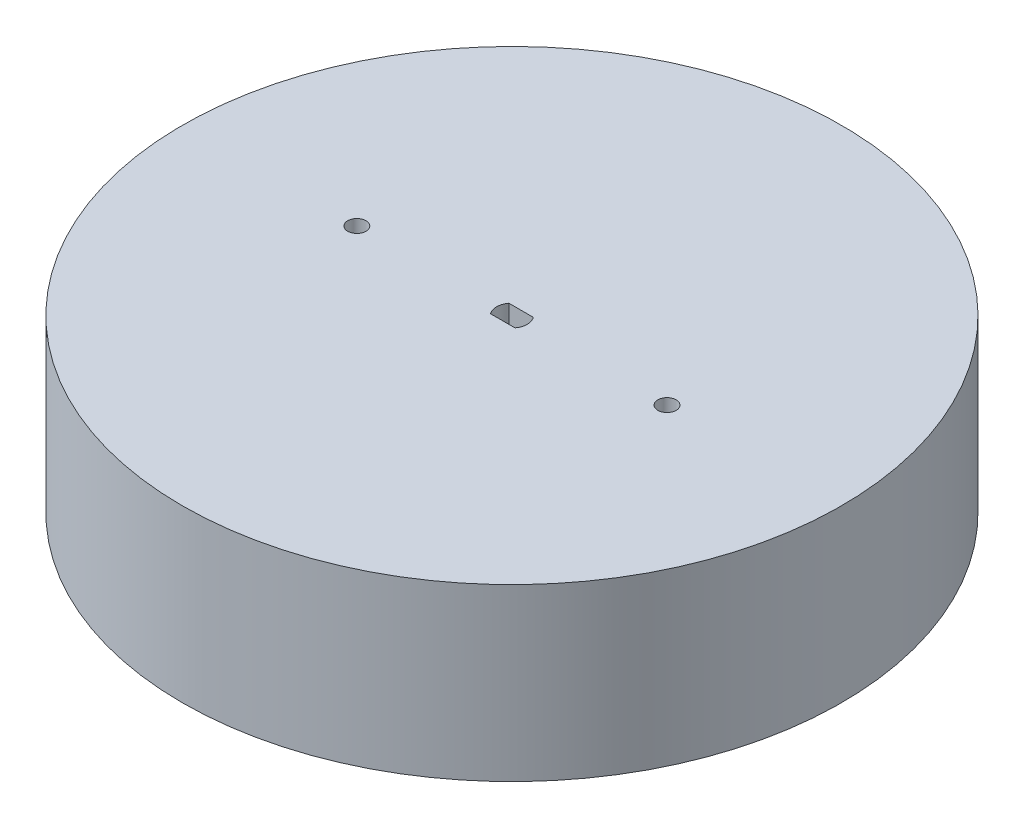
SolidWorks part; units mm, degrees
ref_plane "Front Plane" through (0, 0, 0) normal (0, 0, 1) x (1, 0, 0)
ref_plane "Top Plane" through (0, 0, 0) normal (0, 1, 0) x (1, 0, 0)
ref_plane "Right Plane" through (0, 0, 0) normal (1, 0, 0) x (0, 0, -1)
sketch "Sketch1" plane through (0, 0, 0) normal (0, 1, 0) x (1, 0, 0)
  circle A0 centre (0, 0) radius 47.625
  circle A1 centre (0, 0) radius 53.975
  dimension "D1" = 95.25
  dimension "D2" = 107.95
extrude "Boss-Extrude1" add sketch "Sketch1" along normal blind 8.89 contours A0 | A1 A0 region at (0, 0, 0) region at (-52.4484, 0, 0)
extrude "Boss-Extrude2" add sketch "Sketch1<4>" against normal blind 19.05
sketch "Sketch1<4>" plane through (0, 0, 0) normal (0, 1, 0) x (1, 0, 0) same geometry as "Sketch1"
sketch "Sketch2" plane through (0, 8.89, 0) normal (0, 1, 0) x (1, 0, 0)
  line L0 (-2, 1.5) -> (2, 1.5)
  line L1 (-2, -1.5) -> (2, -1.5)
  arc A0 (2, 1.5) -> (2, -1.5) centre (0, 0) cw
  arc A1 (-2, 1.5) -> (-2, -1.5) centre (0, 0) ccw
extrude "Cut-Extrude1" cut sketch "Sketch2" against normal blind 25.4
sketch "Sketch3" plane through (0, 0, 0) normal (0, -1, 0) x (1, 0, 0)
  circle A0 centre (0, 0) radius 34.925
  circle A1 centre (0, 0) radius 47.625
  circle A2 centre (0, 0) radius 47.625 construction
  dimension "3" = 69.85
extrude "Boss-Extrude3" add sketch "Sketch3" along normal blind 3.4925
sketch "Sketch4" plane through (0, 8.89, 0) normal (0, 1, 0) x (1, 0, 0)
  circle A0 centre (25.4, 0) radius 1.5
  circle A1 centre (-25.4, 0) radius 1.5
  dimension "D1" = 3
  dimension "D2" = 25.4
  dimension "D3" = 25.4
extrude "Cut-Extrude2" cut sketch "Sketch4" against normal blind 21.2725
